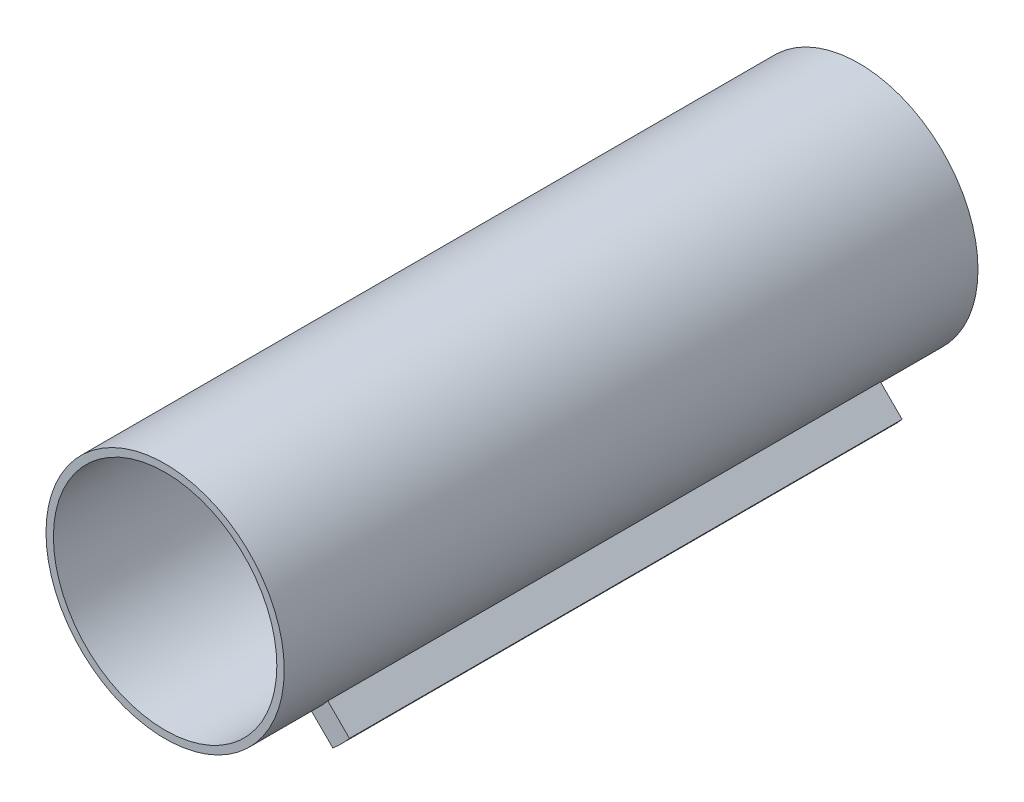
SolidWorks part; units mm, degrees
ref_plane "Front Plane" through (0, 0, 0) normal (0, 0, 1) x (1, 0, 0)
ref_plane "Top Plane" through (0, 0, 0) normal (0, 1, 0) x (1, 0, 0)
ref_plane "Right Plane" through (0, 0, 0) normal (1, 0, 0) x (0, 0, -1)
sketch "Sketch1" plane through (0, 0, 0) normal (0, 0, 1) x (1, 0, 0)
  circle A0 centre (0, 0) radius 95
  circle A1 centre (0, 0) radius 101.3
extrude "Boss-Extrude1" add sketch "Sketch1" along normal blind 590
sketch "Sketch2" plane through (0, 0, 0) normal (0, 0, 1) x (1, 0, 0)
  circle A0 centre (0, 0) radius 110
ref_plane "Plane2" through (0, 0, 60) normal (0, 0, -1) x (-1, 0, 0)
sketch "Sketch6" plane through (0, 0, 60) normal (0, 0, -1) x (-1, 0, 0)
  line L2 (96.7721, -82.63) -> (78.3511, -64.209)
  line L4 (64.209, -78.3511) -> (82.63, -96.7721)
  arc A0 (82.63, -96.7721) -> (96.7721, -82.63) centre (0, 0) ccw
  arc A1 (64.209, -78.3511) -> (78.3511, -64.209) centre (0, 0) ccw
extrude "Boss-Extrude2" add sketch "Sketch6" against normal blind 470
mirror "Mirror1" about plane through (0, 0, 0) normal (1, 0, 0) of "Boss-Extrude2"
